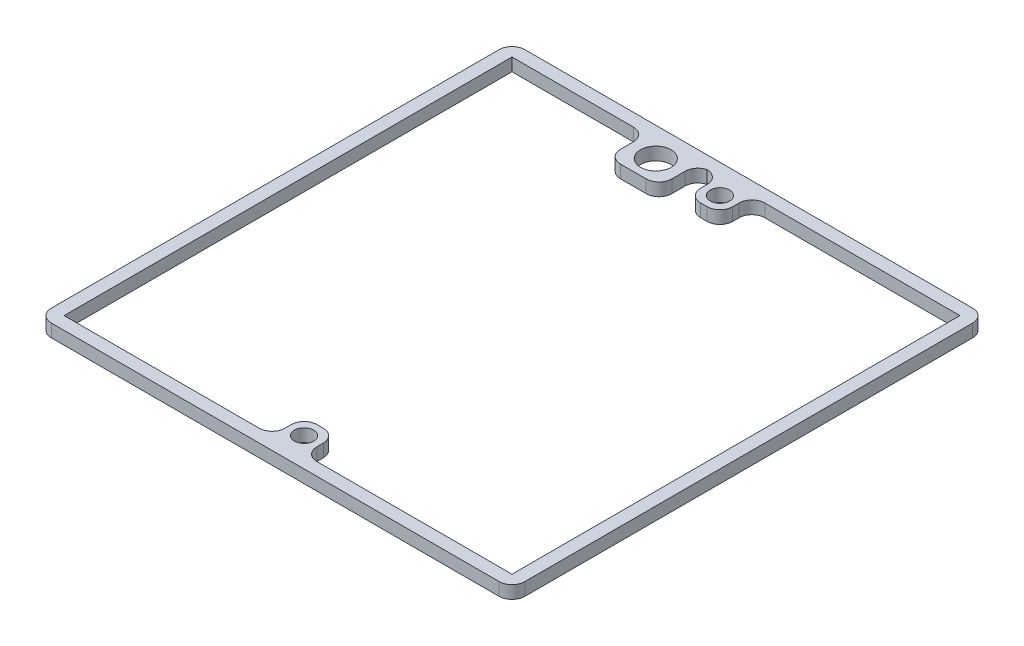
SolidWorks part; units mm, degrees
ref_plane "Front Plane" through (0, 0, 0) normal (0, 0, 1) x (1, 0, 0)
ref_plane "Top Plane" through (0, 0, 0) normal (0, 1, 0) x (1, 0, 0)
ref_plane "Right Plane" through (0, 0, 0) normal (1, 0, 0) x (0, 0, -1)
sketch "Sketch1" plane through (0, 0, 0) normal (0, 1, 0) x (1, 0, 0)
  line L0 (34.925, -34.925) -> (34.925, 34.925)
  line L1 (36.925, -36.925) -> (-36.925, -36.925)
  line L2 (36.925, -36.925) -> (36.925, 36.925)
  line L3 (36.925, 36.925) -> (-36.925, 36.925)
  line L4 (-36.925, -36.925) -> (-36.925, 36.925)
  line L5 (36.925, -36.925) -> (-36.925, 36.925) construction
  line L6 (36.925, 36.925) -> (-36.925, -36.925) construction
  line L7 (34.925, 34.925) -> (-34.925, 34.925)
  line L8 (-34.925, -34.925) -> (-34.925, 34.925)
  line L9 (34.925, -34.925) -> (-34.925, -34.925)
  point P0 (0, 0)
  dimension "D2" = 73.85
  dimension "D3" = 2
extrude "Boss-Extrude1" add sketch "Sketch1" along normal blind 2
sketch "Sketch2" plane through (0, 2, 0) normal (0, 1, 0) x (1, 0, 0)
  line L0 (34.925, 34.925) -> (-34.925, 34.925) construction
  line L1 (34.925, 34.925) -> (-34.925, 34.925)
  line L2 (0, 34.925) -> (0, -34.925) construction
  line L3 (-2.5, 34.925) -> (2.5, 34.925)
  line L4 (36.925, -36.925) -> (36.925, 36.925)
  line L5 (36.925, 36.925) -> (-36.925, 36.925)
  line L6 (-36.925, 36.925) -> (-36.925, -36.925)
  line L7 (-36.925, -36.925) -> (36.925, -36.925)
  line L8 (36.925, -36.925) -> (36.925, 36.925)
  line L9 (36.925, 36.925) -> (-36.925, 36.925)
  line L10 (-36.925, 36.925) -> (-36.925, -36.925)
  line L11 (-36.925, -36.925) -> (36.925, -36.925)
  line L12 (-2.5, 34.925) -> (-2.5, 29.925)
  line L13 (-2.5, 29.925) -> (2.5, 29.925)
  line L14 (2.5, 34.925) -> (2.5, 29.925)
  line L15 (-34.925, -34.925) -> (34.925, -34.925) construction
  line L16 (-34.925, 0) -> (34.925, 0) construction
  line L17 (-34.925, 34.925) -> (-34.925, -34.925) construction
  line L18 (34.925, -34.925) -> (34.925, 34.925) construction
  line L19 (2.5, -34.925) -> (2.5, -29.925)
  line L20 (-2.5, -34.925) -> (2.5, -34.925)
  line L21 (-2.5, -34.925) -> (-2.5, -29.925)
  line L22 (-2.5, -29.925) -> (2.5, -29.925)
  circle A0 centre (0, 32.425) radius 1.5
  circle A1 centre (0, -32.425) radius 1.5
  point P20 (0, 29.925)
  point P34 (-2.5, 32.425)
  line M29 (34.925, -34.925) -> (-34.925, -34.925)
  dimension "D4" = 3
  dimension "D3" = 5
extrude "Boss-Extrude2" add sketch "Sketch2" against normal up to surface (2 mm away) contours L14 L1 L12 L13 A0 | L22 L21 L19 A1 M29 region at (2.4293, 2, -32.425) region at (0, 2, 34.8543) up to face at (0, 0, 0)
fillet "Fillet1" radius 2 12 edges at (36.925, 1, -36.925) (36.925, 1, 36.925) (-36.925, 1, 36.925) (-36.925, 1, -36.925) (-2.5, 1, 29.925) (2.5, 1, 29.925) (2.5, 1, -29.925) (-2.5, 1, -29.925) (-2.5, 1, 34.925) (2.5, 1, 34.925) (2.5, 1, -34.925) (-2.5, 1, -34.925)
sketch "Sketch3" plane through (0, 2, 0) normal (0, 1, 0) x (1, 0, 0)
  line L0 (-4.5, 34.925) -> (-34.925, 34.925) construction
  line L1 (-14, 34.925) -> (-6, 34.925)
  line L2 (-14, 34.925) -> (-14, 28.925)
  line L3 (-14, 28.925) -> (-6, 28.925)
  line L4 (36.925, -34.925) -> (36.925, 34.925)
  line L5 (34.925, 36.925) -> (-34.925, 36.925)
  line L6 (-36.925, 34.925) -> (-36.925, -34.925)
  line L7 (-34.925, -36.925) -> (34.925, -36.925)
  line L8 (36.925, -34.925) -> (36.925, 34.925)
  line L9 (34.925, 36.925) -> (-34.925, 36.925)
  line L10 (-36.925, 34.925) -> (-36.925, -34.925)
  line L11 (-34.925, -36.925) -> (34.925, -36.925)
  line L12 (-6, 34.925) -> (-6, 28.925)
  circle A0 centre (0, 32.425) radius 1.5 construction
  circle A1 centre (0, 32.425) radius 1.5
  circle A2 centre (-10, 32.425) radius 2.3812
  arc A4 (36.925, 34.925) -> (34.925, 36.925) centre (34.925, 34.925) ccw
  arc A5 (-34.925, 36.925) -> (-36.925, 34.925) centre (-34.925, 34.925) ccw
  arc A6 (-36.925, -34.925) -> (-34.925, -36.925) centre (-34.925, -34.925) ccw
  arc A7 (34.925, -36.925) -> (36.925, -34.925) centre (34.925, -34.925) ccw
  arc A8 (36.925, 34.925) -> (34.925, 36.925) centre (34.925, 34.925) ccw
  arc A9 (-34.925, 36.925) -> (-36.925, 34.925) centre (-34.925, 34.925) ccw
  arc A10 (-36.925, -34.925) -> (-34.925, -36.925) centre (-34.925, -34.925) ccw
  arc A11 (34.925, -36.925) -> (36.925, -34.925) centre (34.925, -34.925) ccw
  point P23 (-10, 34.925)
  point P24 (-13.2649, 32.425)
  point P25 (-9.6128, 32.425)
  line M29 (-34.925, 34.925) -> (-4.5, 34.925)
  dimension "D2" = 4.7625
  dimension "D3" = 8
  dimension "D4" = 6
  dimension "D5" = 10
extrude "Boss-Extrude3" add sketch "Sketch3" against normal up to surface (2 mm away) contours L12 L2 L3 A2 M29 region at (-10, 2, -34.825) up to face at (0, 0, 0)
fillet "Fillet2" radius 2 4 edges at (-14, 1, -34.925) (-6, 1, -34.925) (-6, 1, -28.925) (-14, 1, -28.925)
equation "\"D\"=74"
equation "\"D2@Sketch1\"=\"D\"-\"C\""
equation "\"T\"=2"
equation "\"D3@Sketch1\"=\"T\""
equation "\"D1@Boss-Extrude1\"=\"T\""
equation "\"F\"=2"
equation "\"D1@Fillet1\"=\"F\""
equation "\"TAB\"=5"
equation "\"D2@Sketch2\"=\"TAB\""
equation "\"D3@Sketch2\"=\"TAB\""
equation "\"TABH\"=3"
equation "\"D4@Sketch2\"=\"TABH\""
equation "\"C\"= 0.15"
equation "\"OUTPUTTUBE\"=4.7625"
equation "\"D2@Sketch3\"=\"OUTPUTTUBE\""
equation "\"OUTPUTL\"= 8"
equation "\"D3@Sketch3\"=\"OUTPUTL\""
equation "\"OUTPUTW\"= 6"
equation "\"D4@Sketch3\"=\"OUTPUTW\""
equation "\"D1@Fillet2\"=\"F\""
